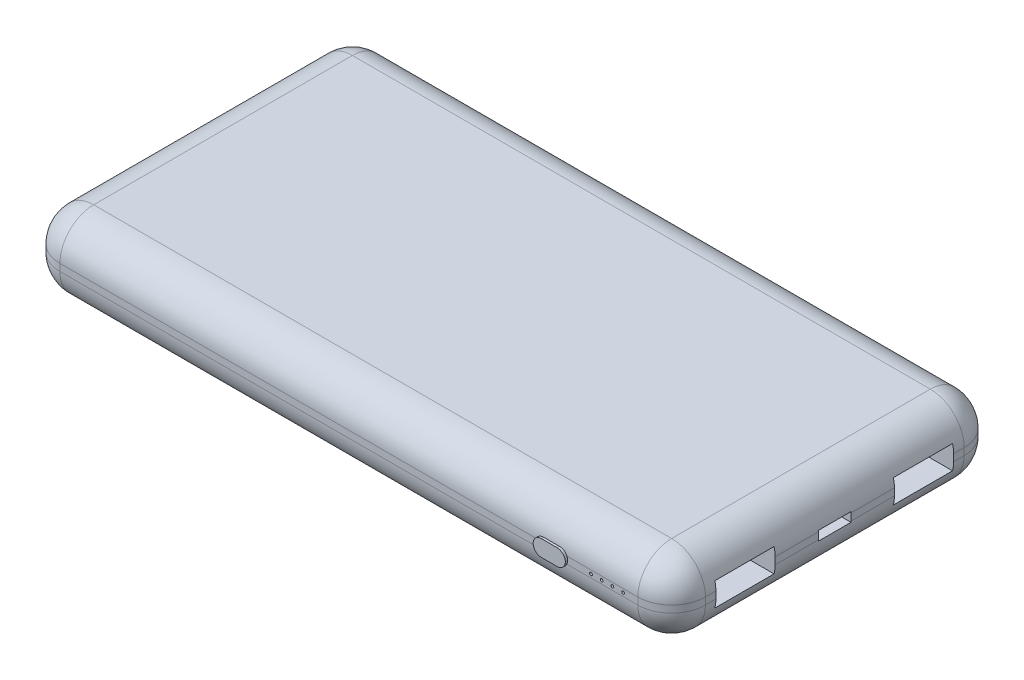
SolidWorks part; units mm, degrees
ref_plane "Front Plane" through (0, 0, 0) normal (0, 0, 1) x (1, 0, 0)
ref_plane "Top Plane" through (0, 0, 0) normal (0, 1, 0) x (1, 0, 0)
ref_plane "Right Plane" through (0, 0, 0) normal (1, 0, 0) x (0, 0, -1)
ref_axis "X Axis" through (-84.3881, 0, 0) along (1, 0, 0)
ref_axis "Y Axis" through (0, 58.113, 0) along (0, -1, 0)
ref_axis "Z Axis" through (0, 0, -88.99) along (0, 0, 1)
sketch "Sketch1" plane through (0, 0, 0) normal (0, 1, 0) x (1, 0, 0)
  line L1 (-69.25, -35) -> (69.25, -35)
  line L2 (-69.25, -35) -> (-69.25, 35)
  line L3 (-69.25, 35) -> (69.25, 35)
  line L4 (69.25, -35) -> (69.25, 35)
  line L5 (-69.25, -35) -> (69.25, 35) construction
  line L6 (-69.25, 35) -> (69.25, -35) construction
  point P0 (0, 0)
  dimension "D1" = 138.5
  dimension "D2" = 70
extrude "Boss-Extrude1" add sketch "Sketch1" along normal mid plane 16
fillet "Fillet1" radius 7.25 12 edges at (-69.25, 0, -35) (69.25, 0, -35) (-69.25, 0, 35) (69.25, 0, 35) (0, -8, -35) (-69.25, -8, 0) (0, -8, 35) (69.25, -8, 0) (0, 8, 35) (-69.25, 8, 0) (0, 8, -35) (69.25, 8, 0)
sketch "Sketch3" plane through (69.25, 0, 0) normal (1, 0, 0) x (0, 0, -1)
  line L0 (-35, -0.75) -> (-35, 0.75) construction
  line L1 (-25.5, -2.54) -> (-12.8, -2.54)
  line L2 (-25.5, -2.54) -> (-25.5, 2.54)
  line L3 (-25.5, 2.54) -> (-12.8, 2.54)
  line L4 (-12.8, -2.54) -> (-12.8, 2.54)
  line L5 (-25.5, -2.54) -> (-12.8, 2.54) construction
  line L6 (-25.5, 2.54) -> (-12.8, -2.54) construction
  line L7 (0, 8.8) -> (0, -8.8) construction
  line L8 (25.5, 2.54) -> (12.8, -2.54) construction
  line L9 (25.5, -2.54) -> (12.8, 2.54) construction
  line L10 (12.8, -2.54) -> (12.8, 2.54)
  line L11 (25.5, 2.54) -> (12.8, 2.54)
  line L12 (25.5, -2.54) -> (25.5, 2.54)
  line L13 (25.5, -2.54) -> (12.8, -2.54)
  point P0 (-19.15, 0)
  point P7 (0, 0)
  point P15 (19.15, 0)
  dimension "D1" = 12.7
  dimension "D2" = 5.08
  dimension "D3" = 9.5
extrude "USB-A" cut sketch "Sketch3" against normal blind 11.25
sketch "Sketch4" plane through (69.25, 0, 0) normal (1, 0, 0) x (0, 0, -1)
  line L1 (-3.5, -1) -> (3.5, -1)
  line L2 (-3.5, -1) -> (-3.5, 1)
  line L3 (-3.5, 1) -> (3.5, 1)
  line L4 (3.5, -1) -> (3.5, 1)
  line L5 (-3.5, -1) -> (3.5, 1) construction
  line L6 (-3.5, 1) -> (3.5, -1) construction
  point P0 (0, 0)
  dimension "D1" = 2
  dimension "D2" = 7
extrude "USB-micro-NOTtoSCALE" cut sketch "Sketch4" against normal blind 5
sketch "Sketch5" plane through (0, 0, -35) normal (0, 0, -1) x (-1, 0, 0)
  line L0 (-69.25, -0.75) -> (-69.25, 0.75) construction
  line L1 (-50.2, -1.27) -> (-41.818, -1.27)
  line L2 (-50.2, -1.27) -> (-50.2, 1.27)
  line L3 (-50.2, 1.27) -> (-41.818, 1.27)
  line L4 (-41.818, -1.27) -> (-41.818, 1.27)
  line L5 (-50.2, -1.27) -> (-41.818, 1.27) construction
  line L6 (-50.2, 1.27) -> (-41.818, -1.27) construction
  point P0 (-46.009, 0)
  point P7 (0, 0)
  dimension "D1" = 19.05
  dimension "D2" = 2.54
  dimension "D3" = 8.382
extrude "USB-C" cut sketch "Sketch5" against normal blind 8
fillet "Fillet2" radius 1.27 4 edges at (41.818, 1.27, -30.9907) (41.818, -1.27, -30.9907) (50.2, -1.27, -30.9907) (50.2, 1.27, -30.9907)
sketch "Sketch6" plane through (0, 0, 35) normal (0, 0, 1) x (1, 0, 0)
  line L0 (69.25, 0.75) -> (69.25, -0.75) construction
  line L1 (40.04, -1.75) -> (46.94, -1.75)
  line L2 (40.04, -1.75) -> (40.04, 1.75)
  line L3 (40.04, 1.75) -> (46.94, 1.75)
  line L4 (46.94, -1.75) -> (46.94, 1.75)
  line L5 (40.04, -1.75) -> (46.94, 1.75) construction
  line L6 (40.04, 1.75) -> (46.94, -1.75) construction
  point P0 (43.49, 0)
  dimension "D1" = 29.21
  dimension "D2" = 6.9
  dimension "D3" = 3.5
extrude "battery level" add sketch "Sketch6" along normal blind 0.5
fillet "Fillet3" radius 1.75 4 edges at (40.04, -1.75, 35.25) (40.04, 1.75, 35.25) (46.94, -1.75, 35.25) (46.94, 1.75, 35.25)
sketch "Sketch7" plane through (0, 0, 35) normal (0, 0, 1) x (1, 0, 0)
  line L0 (51.94, 0.75) -> (51.94, -0.75) construction
  line L1 (62, 0.75) -> (46.7711, 0.75) construction
  line L2 (46.7711, -0.75) -> (62, -0.75) construction
  line L3 (51.94, 0) -> (62, 0) construction
  line L4 (62, -0.75) -> (62, 0.75) construction
  circle A0 centre (51.94, 0) radius 0.3
  circle A1 centre (54.24, 0) radius 0.3
  circle A2 centre (56.54, 0) radius 0.3
  circle A3 centre (58.84, 0) radius 0.3
  dimension "D2" = 0.6
  dimension "D1" = 5
  dimension "D3" = 4
extrude "battery lights" cut sketch "Sketch7" against normal blind 1
